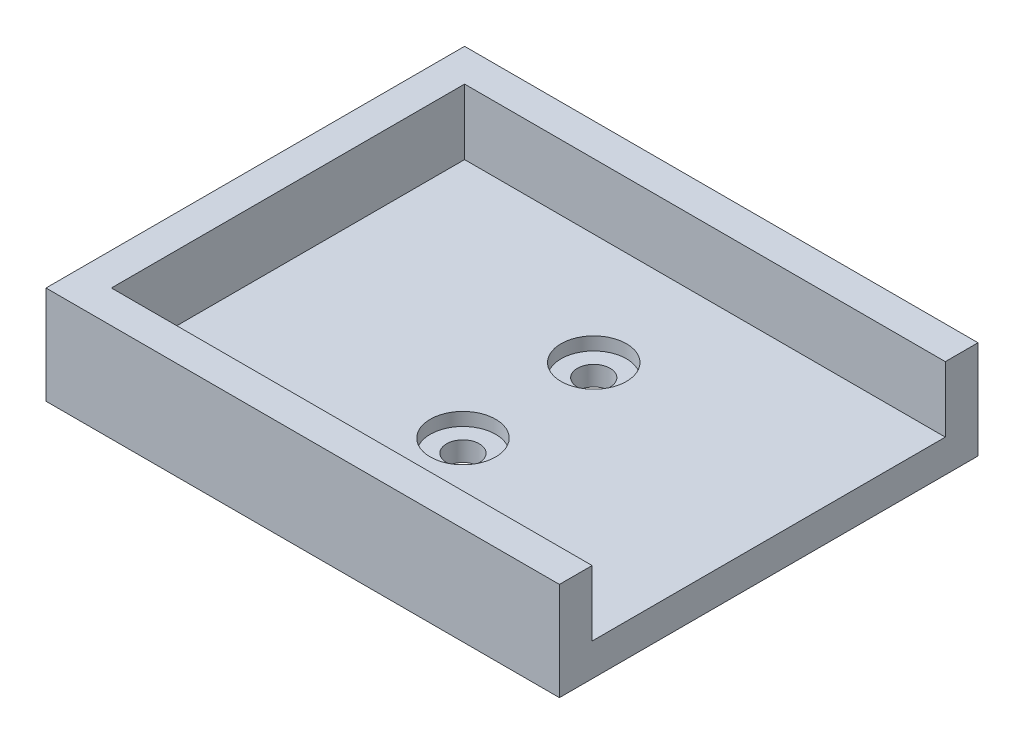
SolidWorks part; units mm, degrees
ref_plane "Front Plane" through (0, 0, 0) normal (0, 0, 1) x (1, 0, 0)
ref_plane "Top Plane" through (0, 0, 0) normal (0, 1, 0) x (1, 0, 0)
ref_plane "Right Plane" through (0, 0, 0) normal (1, 0, 0) x (0, 0, -1)
sketch "Sketch1" plane through (0, 0, 0) normal (0, 1, 0) x (1, 0, 0)
  line L0 (0, 10) -> (0, -10) construction
  circle A0 centre (0, 10) radius 2.5
  circle A1 centre (0, -10) radius 2.5
  circle A2 centre (0, 10) radius 5
  circle A3 centre (0, -10) radius 5
  point P3 (0, 0)
  dimension "D1" = 20
  dimension "D2" = 5
  dimension "D4" = 10
  dimension "D3" = 5
  dimension "D5" = 10
sketch "Sketch3" plane through (0, 0, 0) normal (0, 1, 0) x (1, 0, 0)
  line L0 (0, 10) -> (0, -10) construction
  line L1 (-36.75, 27) -> (36.75, 27)
  line L2 (-36.75, 27) -> (-36.75, -27)
  line L3 (-36.75, -27) -> (36.75, -27)
  line L4 (36.75, 27) -> (36.75, -27)
  line L5 (-36.75, 27) -> (36.75, -27) construction
  line L6 (-36.75, -27) -> (36.75, 27) construction
  point P0 (0, 0)
  dimension "D1" = 73.5
  dimension "D2" = 54
extrude "Boss-Extrude2" add sketch "Sketch3" along normal blind 5
sketch "Sketch4" plane through (0, 0, 0) normal (0, 1, 0) x (1, 0, 0)
  line L13 (-36.75, 27) -> (36.75, 27)
  line L14 (-36.75, 27) -> (-36.75, 32)
  line L15 (-36.75, 32) -> (36.75, 32)
  line L16 (36.75, 27) -> (36.75, 32)
  line L17 (-36.75, -27) -> (36.75, -27)
  line L18 (-36.75, -27) -> (-36.75, -32)
  line L19 (-36.75, -32) -> (36.75, -32)
  line L20 (36.75, -27) -> (36.75, -32)
  line L21 (-36.75, 32) -> (-41.75, 32)
  line L22 (-36.75, 32) -> (-36.75, -32)
  line L23 (-36.75, -32) -> (-41.75, -32)
  line L24 (-41.75, 32) -> (-41.75, -32)
  dimension "D1" = 5
  dimension "D2" = 5
  dimension "D3" = 5
extrude "Boss-Extrude4" add sketch "Sketch4" along normal blind 15 contours L21 L24 L23 L18 L22 L14 | L20 L17 L18 L19 | L15 L16 L13 L14 region at (-39.25, 0, 0) region at (0, 0, 29.5)
ref_plane "Plane1" through (0, 5, 0) normal (0, 1, 0) x (1, 0, 0)
sketch "Sketch6" plane through (0, 5, 0) normal (0, 1, 0) x (1, 0, 0)
  line L0 (0, 10) -> (0, -10) construction
  circle A0 centre (0, 10) radius 5
  circle A1 centre (0, -10) radius 5
  circle A2 centre (0, 10) radius 2.5
  circle A3 centre (0, -10) radius 2.5
  dimension "D1" = 5
  dimension "D2" = 10
  dimension "D3" = 5
  dimension "D4" = 10
extrude "Cut-Extrude4" cut sketch "Sketch6" against normal blind 2
extrude "Cut-Extrude5" cut sketch "Sketch1" along normal blind 10 and the other way through all contours A0
extrude "Cut-Extrude6" cut sketch "Sketch1<7>" along normal blind 10 contours A1
sketch "Sketch1<7>" plane through (0, 0, 0) normal (0, 1, 0) x (1, 0, 0) same geometry as "Sketch1"
